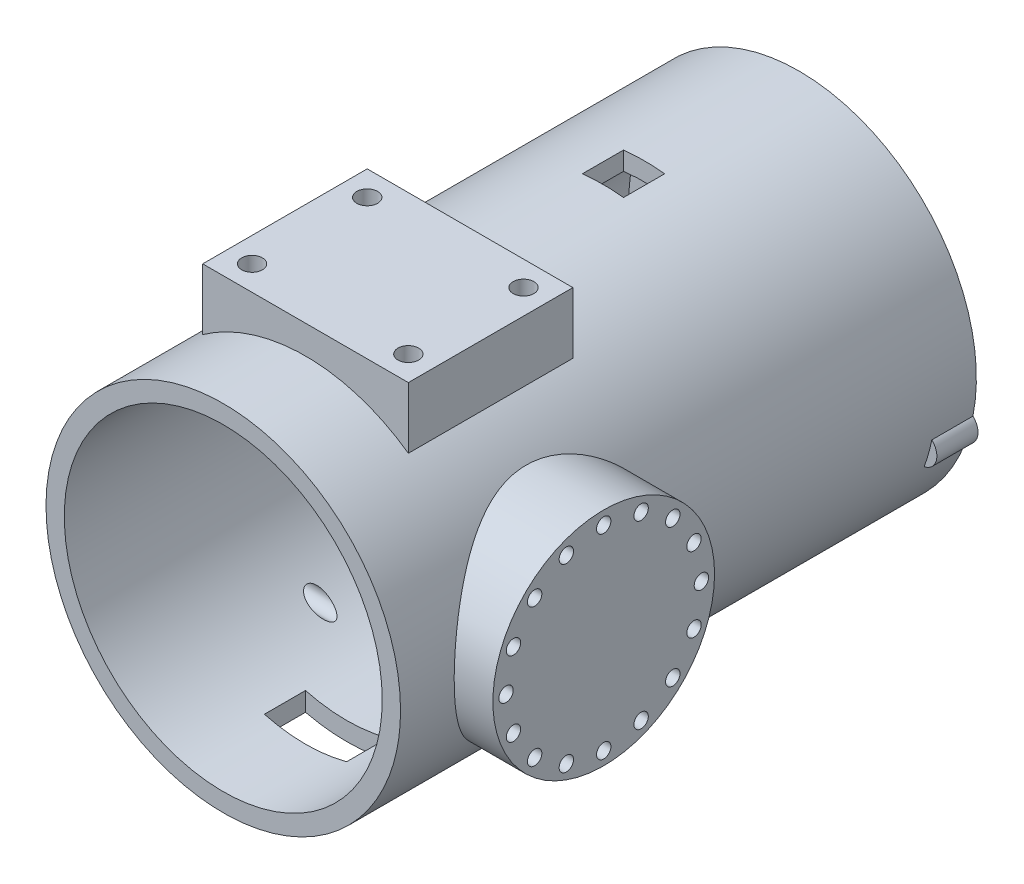
SolidWorks part; units mm, degrees
other "Markup1"
sketch "Sketch14" plane through (-43.1, 43.1, 140) normal (-0.1765, 0.0048, 0.9843) x (0.9842, -0.0149, 0.1765)
other "Markup2"
sketch "Sketch23" plane through (45.1, -43.1, 140) normal (0.9491, -0.0629, 0.3087) x (0.311, 0.031, -0.9499)
ref_plane "Front Plane" through (0, 0, 0) normal (0, 0, 1) x (1, 0, 0)
ref_plane "Top Plane" through (0, 0, 0) normal (0, 1, 0) x (1, 0, 0)
ref_plane "Right Plane" through (0, 0, 0) normal (1, 0, 0) x (0, 0, -1)
sketch "Sketch1" plane through (0, 0, 0) normal (0, 0, 1) x (1, 0, 0)
  circle A1 centre (0, 0) radius 43.1
  dimension "D1" = 86.2
extrude "Main Body" add sketch "Sketch1" along normal blind 140
ref_plane "Plane1" through (0, 43.1, 0) normal (0, 1, 0) x (1, 0, 0)
sketch "Sketch34" [suppressed] plane through (0, 43.1, 0) normal (0, 1, 0) x (1, 0, 0)
  line L6 (-5, -13) -> (5, -13)
  line L8 (-5, -13) -> (-5, -3)
  line L9 (-5, -3) -> (5, -3)
  line L10 (5, -13) -> (5, -3)
  line L11 (-5, -13) -> (5, -3) construction
  line L12 (-5, -3) -> (5, -13) construction
  point P0 (0, -8)
  dimension "D1" = 8
  dimension "D2" = 10
  dimension "D3" = 10
sketch "Sketch6" plane through (0, 43.1, 0) normal (0, 1, 0) x (1, 0, 0)
  line L2 (-5, -47.7) -> (5, -47.7)
  line L3 (-5, -47.7) -> (-5, -37.7)
  line L4 (-5, -37.7) -> (5, -37.7)
  line L5 (5, -47.7) -> (5, -37.7)
  line L6 (-5, -47.7) -> (5, -37.7) construction
  line L7 (-5, -37.7) -> (5, -47.7) construction
  point P2 (0, -42.7)
  dimension "D2" = 10
  dimension "D1" = 42.7
  dimension "D3" = 10
extrude "Cut-Extrude3" cut sketch "Sketch6" against normal through all
ref_plane "Plane2" through (52.5, 0, 0) normal (1, 0, 0) x (0, 0, -1)
sketch "Sketch8" plane through (52.5, 0, 0) normal (1, 0, 0) x (0, 0, -1)
  circle A0 centre (-100, 0) radius 26.95
  dimension "D1" = 53.9
  dimension "D2" = 100
extrude "Boss-Extrude2" add sketch "Sketch8" against normal blind 20
mirror "Mirror1" [suppressed] about plane through (0, 0, 0) normal (1, 0, 0)
ref_plane "Plane3" through (0, 50, 0) normal (0, 1, 0) x (1, 0, 0)
sketch "Sketch33" plane through (0, 50, 0) normal (0, 1, 0) x (1, 0, 0)
  line L1 (-25, -120) -> (25, -120)
  line L2 (-25, -120) -> (-25, -80)
  line L3 (-25, -80) -> (25, -80)
  line L4 (25, -120) -> (25, -80)
  line L5 (-25, -120) -> (25, -80) construction
  line L6 (-25, -80) -> (25, -120) construction
  point P0 (0, -100)
  dimension "D1" = 100
  dimension "D2" = 40
  dimension "D3" = 50
extrude "Boss-Extrude11" add sketch "Sketch33" against normal blind 22
sketch "Sketch35" plane through (0, 50, 0) normal (0, 1, 0) x (1, 0, 0)
  line L0 (-25, -120) -> (-25, -80) construction
  line L1 (25, -120) -> (25, -80) construction
  line L2 (25, -80) -> (-25, -80) construction
  line L3 (-25, -120) -> (25, -120) construction
  circle A0 centre (-19, -86) radius 2.525
  circle A1 centre (19, -86) radius 2.525
  circle A2 centre (-19, -114) radius 2.525
  circle A3 centre (19, -114) radius 2.525
  dimension "D1" = 5.05
  dimension "D2" = 6
  dimension "D3" = 6
  dimension "D4" = 6
  dimension "D5" = 6
extrude "Cut-Extrude14" cut sketch "Sketch35" against normal blind 4
sketch "Sketch5" plane through (0, 0, 140) normal (0, 0, 1) x (1, 0, 0)
  circle A0 centre (0, 0) radius 32
  dimension "D1" = 64
extrude "Hole 1" cut sketch "Sketch5" against normal through all
sketch "Sketch10" plane through (0, 0, 0) normal (0, 1, 0) x (1, 0, 0)
  line L0 (43.1, 0) -> (-43.1, 0) construction
  line L1 (-10, -120) -> (10, -120)
  line L2 (-10, -120) -> (-10, -110)
  line L3 (-10, -110) -> (10, -110)
  line L4 (10, -120) -> (10, -110)
  line L5 (-10, -120) -> (10, -110) construction
  line L6 (-10, -110) -> (10, -120) construction
  point P0 (0, -115)
  point P7 (-10, -115)
  dimension "D1" = 110
  dimension "D2" = 10
  dimension "D3" = 20
extrude "Motor Wire Hole" cut sketch "Sketch10" against normal through all
sketch "Sketch27" plane through (0, 0, 0) normal (1, 0, 0) x (0, 0, -1)
  line L1 (-100, -36.5) -> (-60, -36.5)
  line L2 (-100, -36.5) -> (-100, -27.5)
  line L3 (-100, -27.5) -> (-60, -27.5)
  line L4 (-60, -36.5) -> (-60, -27.5)
  dimension "D1" = 60
  dimension "D2" = 27.5
  dimension "D3" = 40
  dimension "D4" = 9
extrude "Boss-Extrude9" add sketch "Sketch27" along normal blind 33 and the other way blind 33
sketch "Sketch11" plane through (0, 0, 0) normal (1, 0, 0) x (0, 0, -1)
  circle A0 centre (-65, -32) radius 2.25
  circle A1 centre (-95, -32) radius 2.25
  dimension "D3" = 4.5
  dimension "D1" = 65
  dimension "D2" = 32
  dimension "D4" = 30
extrude "Cut-Extrude6" cut sketch "Sketch11" against normal through all both and the other way through all
sketch "Sketch28" plane through (-33, 0, 0) normal (-1, 0, 0) x (0, 0, 1)
  line L0 (62.8927, -28.35) -> (67.1073, -28.35)
  line L1 (67.1073, -28.35) -> (69.2147, -32)
  line L2 (69.2147, -32) -> (67.1073, -35.65)
  line L3 (67.1073, -35.65) -> (62.8927, -35.65)
  line L4 (62.8927, -35.65) -> (60.7853, -32)
  line L6 (60.7853, -32) -> (62.8927, -28.35)
  line L7 (92.8927, -28.35) -> (97.1073, -28.35)
  line L8 (97.1073, -28.35) -> (99.2147, -32)
  line L9 (99.2147, -32) -> (97.1073, -35.65)
  line L10 (97.1073, -35.65) -> (92.8927, -35.65)
  line L11 (92.8927, -35.65) -> (90.7853, -32)
  line L12 (90.7853, -32) -> (92.8927, -28.35)
  circle A0 centre (65, -32) radius 3.65 construction
  circle A1 centre (65, -32) radius 2.25 construction
  circle A2 centre (95, -32) radius 3.65 construction
  circle A3 centre (95, -32) radius 2.25 construction
  dimension "D2" = 7.3
extrude "Cut-Extrude7" cut sketch "Sketch28" against normal blind 3
sketch "Sketch29" plane through (33, 0, 0) normal (1, 0, 0) x (0, 0, -1)
  circle A0 centre (-95, -32) radius 3.6
  circle A1 centre (-65, -32) radius 3.6
  dimension "D1" = 7.2
extrude "Cut-Extrude8" cut sketch "Sketch29" against normal blind 4
sketch "Sketch2" plane through (0, 0, 140) normal (0, 0, 1) x (1, 0, 0)
  circle A0 centre (0, 0) radius 38.65
  dimension "D1" = 77.3
extrude "Cut-Extrude5" cut sketch "Sketch2" against normal blind 135
sketch "Sketch9" plane through (0, 0, 5) normal (0, 0, 1) x (1, 0, 0)
  circle A0 centre (0, 0) radius 38.1
  circle A1 centre (0, 0) radius 36.44
  dimension "D1" = 76.2
  dimension "D2" = 1.66
extrude "Boss-Extrude3" add sketch "Sketch9" along normal blind 10
extrude "Cut-Extrude13" [suppressed] cut sketch "Sketch34" against normal blind 15
sketch "Sketch30" plane through (52.5, 0, 0) normal (1, 0, 0) x (0, 0, -1)
  line L0 (-100, 23.75) -> (-100, 0) construction
  circle A0 centre (-100, 0) radius 23.75 construction
  circle A1 centre (-100, 23.75) radius 1.75
  circle A2 centre (-90.9113, 21.9421) radius 1.75
  circle A3 centre (-83.2062, 16.7938) radius 1.75
  circle A4 centre (-78.0579, 9.0887) radius 1.75
  circle A5 centre (-76.25, 0) radius 1.75
  circle A6 centre (-78.0579, -9.0887) radius 1.75
  circle A7 centre (-83.2062, -16.7938) radius 1.75
  circle A8 centre (-90.9113, -21.9421) radius 1.75
  circle A9 centre (-100, -23.75) radius 1.75
  circle A10 centre (-109.0887, -21.9421) radius 1.75
  circle A11 centre (-116.7938, -16.7938) radius 1.75
  circle A12 centre (-121.9421, -9.0887) radius 1.75
  circle A13 centre (-123.75, 0) radius 1.75
  circle A14 centre (-121.9421, 9.0887) radius 1.75
  circle A15 centre (-116.7938, 16.7938) radius 1.75
  circle A16 centre (-109.0887, 21.9421) radius 1.75
  point P38 (-100, 0)
  dimension "D1" = 47.5
  dimension "D2" = 3.5
  dimension "D3" = 16
extrude "Cut-Extrude9" cut sketch "Sketch30" against normal up to surface (22.008 mm away) up to face at (21.7413, -31.9552, 97.2496)
sketch "Sketch31" plane through (52.5, 0, 0) normal (1, 0, 0) x (0, 0, -1)
  line L0 (0, -43.1) -> (0, 43.1) construction
  line L1 (0, -15) -> (-10, -15)
  line L2 (0, -15) -> (0, -7.5)
  line L3 (0, -7.5) -> (-10, -7.5)
  line L4 (-10, -15) -> (-10, -7.5)
  dimension "D1" = 15
  dimension "D2" = 7.5
  dimension "D3" = 10
extrude "Boss-Extrude10" add sketch "Sketch31" against normal up to body from offset 9 offset against normal yes
sketch "Sketch32" plane through (0, 0, 0) normal (0, 0, -1) x (-1, 0, 0)
  line L0 (-43.5, -11.25) -> (-29.9573, -11.25) construction
  line L1 (-43.5, -15) -> (-43.5, -7.5) construction
  line L3 (-42.4424, -7.5) -> (-43.5, -7.5) construction
  line L5 (-43.5, -15) -> (-43.5, -7.5)
  line L6 (-43.5, -7.5) -> (-42.4424, -7.5)
  circle A0 centre (0, 0) radius 32 construction
  arc A2 (-40.4056, -15) -> (-42.4424, -7.5) centre (0, 0) ccw construction
  arc A3 (-40.4056, -15) -> (-42.2658, -8.4385) centre (-39.6806, -11.25) cw
  arc A4 (-42.2658, -8.4385) -> (-42.4424, -7.5) centre (0, 0) cw
  line M3 (-42.4424, -7.5) -> (-43.5, -7.5)
  line M4 (-43.5, -7.5) -> (-43.5, -15)
  line M5 (-43.5, -15) -> (-40.4056, -15)
extrude "Cut-Extrude10" cut sketch "Sketch32" against normal up to surface (10 mm away) contours M4 M3 | L5 M5 region at (43.0347, -8.5479, 0) region at (42.7123, -14.1508, 0) up to face at (42.5043, -11.2615, 10)
